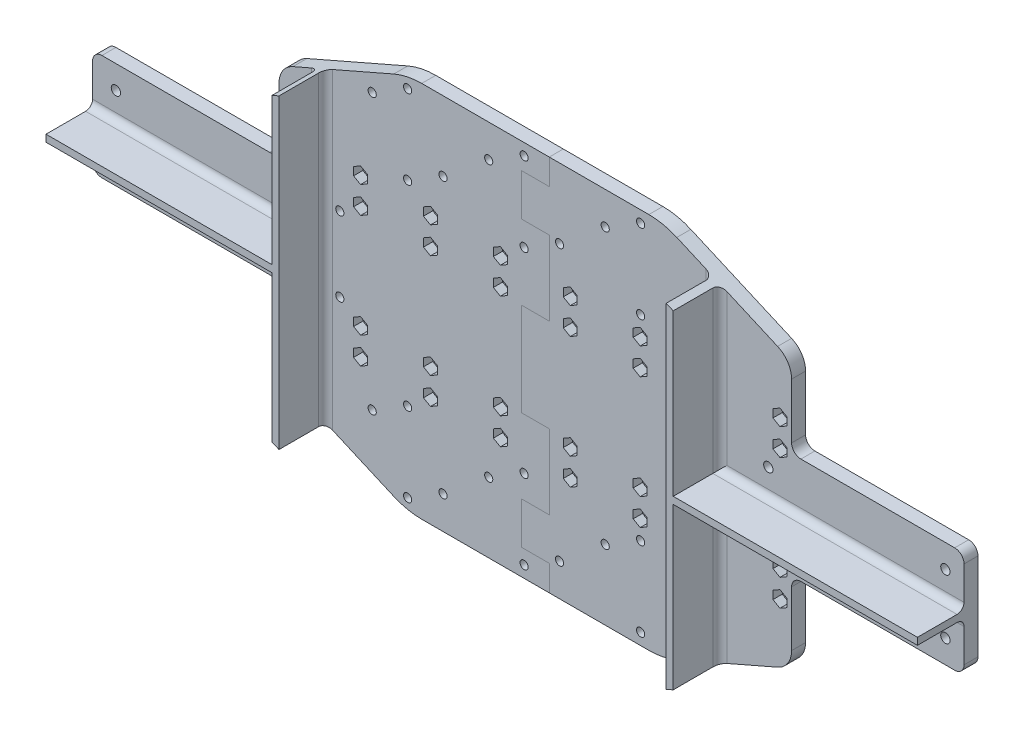
SolidWorks part; units mm, degrees
ref_plane "Top Plane" through (0, 0, 0) normal (0, 0, 1) x (1, 0, 0)
ref_plane "Right Plane" through (0, 0, 0) normal (0, 1, 0) x (1, 0, 0)
ref_plane "Front Plane" through (0, 0, 0) normal (1, 0, 0) x (0, 0, -1)
sketch "Sketch1" plane through (0, 0, 0) normal (0, 0, 1) x (1, 0, 0)
  line L0 (-187, 81) -> (187, -81) construction
  line L1 (-187, 81) -> (187, 81) construction
  line L2 (-187, 81) -> (-187, -81) construction
  line L3 (-187, -81) -> (187, -81) construction
  line L4 (187, 81) -> (187, -81) construction
  line L5 (-187, -22.75) -> (-107, -22.75) construction
  line L6 (-107, -22.75) -> (-107, -81) construction
  line L7 (113, -81) -> (113, -22.75) construction
  line L8 (113, -22.75) -> (187, -22.75) construction
  line L9 (-187, 0) -> (187, 0) construction
  line L10 (113, 22.75) -> (187, 22.75) construction
  line L11 (113, 81) -> (113, 22.75) construction
  line L12 (-107, 22.75) -> (-107, 81) construction
  line L13 (-187, 22.75) -> (-107, 22.75) construction
  line L14 (85.2, -81) -> (85.2, 81) construction
  line L15 (-93, -81) -> (-93, 81) construction
  line L16 (-187, -2.75) -> (187, -2.75) construction
  line L17 (187, 2.75) -> (-187, 2.75) construction
  text T0 "FRONT" font "Century Gothic" height in points 80
  dimension "D1" = 374
  dimension "D2" = 162
  dimension "D3" = 45.5
  dimension "D4" = 80
  dimension "D5" = 74
  dimension "D6" = 27.8
  dimension "D7" = 14
  dimension "D8" = 20
  dimension "D9" = 20
sketch "Sketch2" plane through (0, 0, 0) normal (0, 0, 1) x (1, 0, 0)
  line L0 (-187, 81) -> (-187, -81) construction
  line L1 (-187, 81) -> (187, 81) construction
  line L2 (187, 81) -> (187, -81) construction
  line L3 (-187, -81) -> (187, -81) construction
  line L4 (113, -81) -> (113, -22.75) construction
  line L5 (113, -22.75) -> (187, -22.75) construction
  line L6 (113, 22.75) -> (187, 22.75) construction
  line L7 (113, 81) -> (113, 22.75) construction
  line L8 (-107, 22.75) -> (-107, 81) construction
  line L9 (-187, 22.75) -> (-107, 22.75) construction
  line L10 (-107, -22.75) -> (-107, -81) construction
  line L11 (-187, -22.75) -> (-107, -22.75) construction
  line L12 (-187, 22.75) -> (-187, -22.75)
  line L13 (-107, 81) -> (113, 81)
  line L14 (187, 22.75) -> (187, -22.75)
  line L15 (-107, -81) -> (113, -81)
  line L16 (113, -81) -> (113, -22.75)
  line L17 (113, -22.75) -> (187, -22.75)
  line L18 (113, 22.75) -> (187, 22.75)
  line L19 (113, 81) -> (113, 22.75)
  line L20 (-107, 22.75) -> (-107, 81)
  line L21 (-187, 22.75) -> (-107, 22.75)
  line L22 (-107, -22.75) -> (-107, -81)
  line L23 (-187, -22.75) -> (-107, -22.75)
extrude "Boss-Extrude1" add sketch "Sketch2" along normal mid plane 6
sketch "Sketch3" plane through (0, 0, 3) normal (0, 0, 1) x (1, 0, 0)
  line L0 (-187, -1.5) -> (-90, -1.5)
  line L1 (-187, 81) -> (-187, -81) construction
  line L2 (187, 81) -> (187, -81) construction
  line L3 (-187, 0) -> (187, 0) construction
  line L4 (-187, 0) -> (187, 0) construction
  line L5 (-187, 1.5) -> (-90, 1.5)
  line L6 (-90, 81) -> (-90, 1.5)
  line L7 (-187, 81) -> (187, 81) construction
  line L8 (82.2, -81) -> (82.2, -1.5)
  line L9 (85.2, -81) -> (85.2, 81) construction
  line L10 (-93, -81) -> (-93, 81) construction
  line L11 (-87, -81) -> (-87, 81)
  line L12 (-187, -81) -> (187, -81) construction
  line L13 (79.2, -81) -> (79.2, 81)
  line L14 (79.2, -81) -> (82.2, -81)
  line L15 (79.2, 81) -> (82.2, 81)
  line L16 (-90, 81) -> (-87, 81)
  line L17 (-90, -81) -> (-87, -81)
  line L20 (82.2, 1.5) -> (187, 1.5)
  line L21 (82.2, -1.5) -> (187, -1.5)
  line L22 (82.2, 1.5) -> (82.2, 81)
  line L23 (-90, -1.5) -> (-90, -81)
  line L24 (187, -1.5) -> (187, 1.5)
  line L25 (-187, -1.5) -> (-187, 1.5)
  point P34 (-87, 0)
  point P35 (79.2, 0)
  dimension "D1" = 3
  dimension "D2" = 3
  dimension "D3" = 3
  dimension "D4" = 3
extrude "Boss-Extrude2" add sketch "Sketch3" along normal blind 20
sketch "Sketch4" plane through (0, 0, 3) normal (0, 0, 1) x (1, 0, 0)
  line L0 (-17, -67) -> (13.4, -67) construction
  line L1 (-67, -67) -> (-36.6, -67) construction
  line L2 (-67, -67) -> (-67, -51) construction
  line L3 (-67, -51) -> (-36.6, -51) construction
  line L4 (-36.6, -67) -> (-36.6, -51) construction
  line L5 (-17, -67) -> (-17, -51) construction
  line L6 (-17, -51) -> (13.4, -51) construction
  line L7 (13.4, -67) -> (13.4, -51) construction
  line L8 (33, -67) -> (63.4, -67) construction
  line L9 (33, -67) -> (33, -51) construction
  line L10 (33, -51) -> (63.4, -51) construction
  line L11 (63.4, -67) -> (63.4, -51) construction
  line L12 (-36.6, -67) -> (13.4, -67) construction
  line L13 (-107, -22.75) -> (-107, -81) construction
  line L14 (-67, 59) -> (63.4, 59) construction
  line L15 (-187, -81) -> (187, -81) construction
  line L16 (-187, 0) -> (187, 0) construction
  line L17 (-187, 0) -> (187, 0) construction
  line L18 (-36.6, 67) -> (13.4, 67) construction
  line L19 (63.4, 67) -> (63.4, 51) construction
  line L20 (33, 51) -> (63.4, 51) construction
  line L21 (33, 67) -> (33, 51) construction
  line L22 (33, 67) -> (63.4, 67) construction
  line L23 (13.4, 67) -> (13.4, 51) construction
  line L24 (-17, 51) -> (13.4, 51) construction
  line L25 (-17, 67) -> (-17, 51) construction
  line L26 (-36.6, 67) -> (-36.6, 51) construction
  line L27 (-67, 51) -> (-36.6, 51) construction
  line L28 (-67, 67) -> (-67, 51) construction
  line L29 (-67, 67) -> (-36.6, 67) construction
  line L30 (-17, 67) -> (13.4, 67) construction
  circle A0 centre (-36.6, -67) radius 1.75
  circle A1 centre (-67, -51) radius 1.75
  circle A2 centre (13.4, -67) radius 1.75
  circle A3 centre (-17, -51) radius 1.75
  circle A4 centre (63.4, -67) radius 1.75
  circle A5 centre (33, -51) radius 1.75
  circle A6 centre (33, 51) radius 1.75 construction
  circle A7 centre (63.4, 67) radius 1.75 construction
  circle A8 centre (-17, 51) radius 1.75 construction
  circle A9 centre (13.4, 67) radius 1.75 construction
  circle A10 centre (-67, 51) radius 1.75 construction
  circle A11 centre (-36.6, 67) radius 1.75 construction
  circle A12 centre (33, 67) radius 1.75
  circle A13 centre (63.4, 51) radius 1.75
  circle A14 centre (13.4, 51) radius 1.75
  circle A15 centre (-17, 67) radius 1.75
  circle A16 centre (-36.6, 51) radius 1.75
  circle A17 centre (-67, 67) radius 1.75
  dimension "D3" = 3.5
  dimension "D1" = 16
  dimension "D2" = 30.4
  dimension "D5" = 50
  dimension "D6" = 40
  dimension "D7" = 14
  dimension "D4" = 3
extrude "Cut-Extrude1" cut sketch "Sketch4" against normal through all
fillet "Fillet1" radius 4 4 edges at (-107, 22.75, 0) (-107, -22.75, 0) (113, -22.75, 0) (113, 22.75, 0)
fillet "Fillet2" radius 3 10 edges at (-90, 41.25, 3) (-138.5, 1.5, 3) (-138.5, -1.5, 3) (-90, -41.25, 3) (82.2, -41.25, 3) (134.6, -1.5, 3) (134.6, 1.5, 3) (82.2, 41.25, 3) (-87, 0, 3) (79.2, 0, 3)
sketch "Sketch5" plane through (0, 0, -3) normal (0, 0, -1) x (-1, 0, 0)
  circle A0 centre (-103, -12.75) radius 2 construction
  circle A1 centre (-103, 12.75) radius 2 construction
  circle A2 centre (-179, 12.75) radius 2 construction
  circle A3 centre (-179, -12.75) radius 2 construction
  circle A4 centre (177, 12.75) radius 2 construction
  circle A5 centre (177, -12.75) radius 2 construction
  circle A6 centre (101, -12.75) radius 2 construction
  circle A7 centre (101, 12.75) radius 2 construction
  circle A8 centre (-103, -12.75) radius 2
  circle A9 centre (-103, 12.75) radius 2
  circle A10 centre (-179, 12.75) radius 2
  circle A11 centre (-179, -12.75) radius 2
  circle A12 centre (177, 12.75) radius 2
  circle A13 centre (177, -12.75) radius 2
  circle A14 centre (101, -12.75) radius 2
  circle A15 centre (101, 12.75) radius 2
extrude "Cut-Extrude2" cut sketch "Sketch5" against normal up to next
sketch "Sketch6" plane through (0, 0, 3) normal (0, 0, 1) x (1, 0, 0)
  line L0 (-67, -67) -> (-36.6, -51) construction
  line L1 (-51.8, -76) -> (-51.8, -42) construction
  line L2 (-67, -59) -> (-36.6, -59) construction
  line L3 (-67, -67) -> (-67, -51) construction
  line L4 (-36.6, -67) -> (-36.6, -51) construction
  line L5 (-1.8, -76) -> (-1.8, -42) construction
  line L6 (48.2, -76) -> (48.2, -42) construction
  line L7 (-51.8, -59) -> (-1.8, -59) construction
  line L8 (-187, 0) -> (187, 0) construction
  line L9 (-187, 0) -> (187, 0) construction
  line L10 (-51.8, 59) -> (-1.8, 59) construction
  line L11 (48.2, 76) -> (48.2, 42) construction
  line L12 (-1.8, 76) -> (-1.8, 42) construction
  line L13 (-67, 59) -> (-36.6, 59) construction
  line L14 (-51.8, 76) -> (-51.8, 42) construction
  line L15 (-67, 67) -> (-36.6, 51) construction
  circle A0 centre (-51.8, -76) radius 1.75
  circle A1 centre (-51.8, -42) radius 1.75
  circle A2 centre (-1.8, -76) radius 1.75
  circle A3 centre (-1.8, -42) radius 1.75
  circle A4 centre (48.2, -76) radius 1.75
  circle A5 centre (48.2, -42) radius 1.75
  circle A6 centre (48.2, 42) radius 1.75
  circle A7 centre (48.2, 76) radius 1.75
  circle A8 centre (-1.8, 42) radius 1.75
  circle A9 centre (-1.8, 76) radius 1.75
  circle A10 centre (-51.8, 42) radius 1.75
  circle A11 centre (-51.8, 76) radius 1.75
  point P4 (-51.8, -59)
  point P17 (-1.8, -59)
  point P22 (48.2, -59)
  point P47 (48.2, 59)
  dimension "D1" = 3.5
  dimension "D2" = 34
  dimension "D4" = 50
  dimension "D3" = 3
extrude "Cut-Extrude3" cut sketch "Sketch6" against normal through all
sketch "Sketch8" plane through (0, 0, 3) normal (0, 0, 1) x (1, 0, 0)
  line L0 (-80.9, -16) -> (73.1, 16) construction
  line L1 (-80.9, -16) -> (73.1, -16) construction
  line L2 (-80.9, -16) -> (-80.9, 16) construction
  line L3 (-80.9, 16) -> (73.1, 16) construction
  line L4 (73.1, -16) -> (73.1, 16) construction
  line L5 (-187, 0) -> (187, 0) construction
  line L6 (-187, 0) -> (187, 0) construction
  line L7 (-3.9, -21.9049) -> (-3.9, 21.9049) construction
  line L8 (-93, -81) -> (85.2, 81) construction
  circle A0 centre (-80.9, -16) radius 1.75
  circle A1 centre (-80.9, 16) radius 1.75
  circle A2 centre (73.1, 16) radius 1.75
  circle A3 centre (73.1, -16) radius 1.75
  point P7 (-3.9, 0)
  dimension "D3" = 3.5
  dimension "D1" = 32
  dimension "D2" = 154
extrude "Cut-Extrude5" cut sketch "Sketch8" against normal through all
sketch "Sketch9" plane through (0, 0, 3) normal (0, 0, 1) x (1, 0, 0)
  line L0 (-107.9535, -28) -> (101.269, -28) construction
  line L1 (-12, -33.75) -> (18, -33.75) construction
  line L2 (-12, -22.25) -> (-42, -22.25) construction
  line L3 (-12, -22.25) -> (18, -22.25) construction
  line L4 (-194.5845, 0) -> (205.1662, 0) construction
  line L5 (3, -92.4344) -> (3, 92.4344) construction
  line L6 (-12, -33.75) -> (-42, -33.75) construction
  line L7 (-107, 81) -> (113, -81) construction
  line L8 (-45, -32.0179) -> (-45, -35.4821) construction
  line L9 (-15, -35.4821) -> (-12, -37.2141) construction
  line L10 (-12, -37.2141) -> (-9, -35.4821) construction
  line L11 (-9, -35.4821) -> (-9, -32.0179) construction
  line L12 (-9, -32.0179) -> (-12, -30.2859) construction
  line L13 (-12, -30.2859) -> (-15, -32.0179) construction
  line L14 (-15, -32.0179) -> (-15, -35.4821) construction
  line L15 (-45, -35.4821) -> (-42, -37.2141) construction
  line L16 (-42, -37.2141) -> (-39, -35.4821) construction
  line L17 (-39, -35.4821) -> (-39, -32.0179) construction
  line L18 (-39, -32.0179) -> (-42, -30.2859) construction
  line L19 (-42, -30.2859) -> (-45, -32.0179) construction
  line L20 (-75, -32.0179) -> (-75, -35.4821) construction
  line L21 (-75, -35.4821) -> (-72, -37.2141) construction
  line L22 (-72, -37.2141) -> (-69, -35.4821) construction
  line L23 (-69, -35.4821) -> (-69, -32.0179) construction
  line L24 (-69, -32.0179) -> (-72, -30.2859) construction
  line L25 (-72, -30.2859) -> (-75, -32.0179) construction
  line L26 (-105, -32.0179) -> (-105, -35.4821) construction
  line L27 (-105, -35.4821) -> (-102, -37.2141) construction
  line L28 (-102, -37.2141) -> (-99, -35.4821) construction
  line L29 (-99, -35.4821) -> (-99, -32.0179) construction
  line L30 (-99, -32.0179) -> (-102, -30.2859) construction
  line L31 (-102, -30.2859) -> (-105, -32.0179) construction
  line L32 (-45, -35.4821) -> (-39, -32.0179) construction
  line L33 (-42, -33.75) -> (-12, -33.75) construction
  line L34 (-12, -25.7141) -> (-15, -23.9821) construction
  line L35 (-9, -23.9821) -> (-12, -25.7141) construction
  line L36 (-9, -20.5179) -> (-9, -23.9821) construction
  line L37 (-12, -18.7859) -> (-9, -20.5179) construction
  line L38 (-15, -20.5179) -> (-12, -18.7859) construction
  line L39 (-15, -23.9821) -> (-15, -20.5179) construction
  line L40 (-39, -20.5179) -> (-39, -23.9821) construction
  line L41 (-42, -18.7859) -> (-39, -20.5179) construction
  line L42 (-45, -20.5179) -> (-42, -18.7859) construction
  line L43 (-45, -23.9821) -> (-45, -20.5179) construction
  line L44 (-42, -25.7141) -> (-45, -23.9821) construction
  line L45 (-39, -23.9821) -> (-42, -25.7141) construction
  line L46 (-69, -20.5179) -> (-69, -23.9821) construction
  line L47 (-72, -18.7859) -> (-69, -20.5179) construction
  line L48 (-75, -20.5179) -> (-72, -18.7859) construction
  line L49 (-75, -23.9821) -> (-75, -20.5179) construction
  line L50 (-72, -25.7141) -> (-75, -23.9821) construction
  line L51 (-69, -23.9821) -> (-72, -25.7141) construction
  line L52 (-99, -20.5179) -> (-99, -23.9821) construction
  line L53 (-102, -18.7859) -> (-99, -20.5179) construction
  line L54 (-105, -20.5179) -> (-102, -18.7859) construction
  line L55 (-105, -23.9821) -> (-105, -20.5179) construction
  line L56 (-102, -25.7141) -> (-105, -23.9821) construction
  line L57 (-99, -23.9821) -> (-102, -25.7141) construction
  line L58 (105, -23.9821) -> (108, -25.7141) construction
  line L59 (108, -25.7141) -> (111, -23.9821) construction
  line L60 (111, -23.9821) -> (111, -20.5179) construction
  line L61 (111, -20.5179) -> (108, -18.7859) construction
  line L62 (108, -18.7859) -> (105, -20.5179) construction
  line L63 (105, -20.5179) -> (105, -23.9821) construction
  line L64 (75, -23.9821) -> (78, -25.7141) construction
  line L65 (78, -25.7141) -> (81, -23.9821) construction
  line L66 (81, -23.9821) -> (81, -20.5179) construction
  line L67 (81, -20.5179) -> (78, -18.7859) construction
  line L68 (78, -18.7859) -> (75, -20.5179) construction
  line L69 (75, -20.5179) -> (75, -23.9821) construction
  line L70 (45, -23.9821) -> (48, -25.7141) construction
  line L71 (48, -25.7141) -> (51, -23.9821) construction
  line L72 (51, -23.9821) -> (51, -20.5179) construction
  line L73 (51, -20.5179) -> (48, -18.7859) construction
  line L74 (48, -18.7859) -> (45, -20.5179) construction
  line L75 (45, -20.5179) -> (45, -23.9821) construction
  line L76 (21, -23.9821) -> (21, -20.5179) construction
  line L77 (21, -20.5179) -> (18, -18.7859) construction
  line L78 (18, -18.7859) -> (15, -20.5179) construction
  line L79 (15, -20.5179) -> (15, -23.9821) construction
  line L80 (15, -23.9821) -> (18, -25.7141) construction
  line L81 (18, -25.7141) -> (21, -23.9821) construction
  line L82 (48, -33.75) -> (18, -33.75) construction
  line L83 (51, -35.4821) -> (45, -32.0179) construction
  line L84 (108, -30.2859) -> (111, -32.0179) construction
  line L85 (105, -32.0179) -> (108, -30.2859) construction
  line L86 (105, -35.4821) -> (105, -32.0179) construction
  line L87 (108, -37.2141) -> (105, -35.4821) construction
  line L88 (111, -35.4821) -> (108, -37.2141) construction
  line L89 (111, -32.0179) -> (111, -35.4821) construction
  line L90 (78, -30.2859) -> (81, -32.0179) construction
  line L91 (75, -32.0179) -> (78, -30.2859) construction
  line L92 (75, -35.4821) -> (75, -32.0179) construction
  line L93 (78, -37.2141) -> (75, -35.4821) construction
  line L94 (81, -35.4821) -> (78, -37.2141) construction
  line L95 (81, -32.0179) -> (81, -35.4821) construction
  line L96 (48, -30.2859) -> (51, -32.0179) construction
  line L97 (45, -32.0179) -> (48, -30.2859) construction
  line L98 (45, -35.4821) -> (45, -32.0179) construction
  line L99 (48, -37.2141) -> (45, -35.4821) construction
  line L100 (51, -35.4821) -> (48, -37.2141) construction
  line L101 (21, -32.0179) -> (21, -35.4821) construction
  line L102 (18, -30.2859) -> (21, -32.0179) construction
  line L103 (15, -32.0179) -> (18, -30.2859) construction
  line L104 (15, -35.4821) -> (15, -32.0179) construction
  line L105 (18, -37.2141) -> (15, -35.4821) construction
  line L106 (21, -35.4821) -> (18, -37.2141) construction
  line L107 (51, -32.0179) -> (51, -35.4821) construction
  line L108 (51, 32.0179) -> (51, 35.4821) construction
  line L109 (21, 35.4821) -> (18, 37.2141) construction
  line L110 (18, 37.2141) -> (15, 35.4821) construction
  line L111 (15, 35.4821) -> (15, 32.0179) construction
  line L112 (15, 32.0179) -> (18, 30.2859) construction
  line L113 (18, 30.2859) -> (21, 32.0179) construction
  line L114 (21, 32.0179) -> (21, 35.4821) construction
  line L115 (51, 35.4821) -> (48, 37.2141) construction
  line L116 (48, 37.2141) -> (45, 35.4821) construction
  line L117 (45, 35.4821) -> (45, 32.0179) construction
  line L118 (45, 32.0179) -> (48, 30.2859) construction
  line L119 (48, 30.2859) -> (51, 32.0179) construction
  line L120 (81, 32.0179) -> (81, 35.4821) construction
  line L121 (81, 35.4821) -> (78, 37.2141) construction
  line L122 (78, 37.2141) -> (75, 35.4821) construction
  line L123 (75, 35.4821) -> (75, 32.0179) construction
  line L124 (75, 32.0179) -> (78, 30.2859) construction
  line L125 (78, 30.2859) -> (81, 32.0179) construction
  line L126 (111, 32.0179) -> (111, 35.4821) construction
  line L127 (111, 35.4821) -> (108, 37.2141) construction
  line L128 (108, 37.2141) -> (105, 35.4821) construction
  line L129 (105, 35.4821) -> (105, 32.0179) construction
  line L130 (105, 32.0179) -> (108, 30.2859) construction
  line L131 (108, 30.2859) -> (111, 32.0179) construction
  line L132 (51, 35.4821) -> (45, 32.0179) construction
  line L133 (48, 33.75) -> (18, 33.75) construction
  line L134 (18, 25.7141) -> (21, 23.9821) construction
  line L135 (15, 23.9821) -> (18, 25.7141) construction
  line L136 (15, 20.5179) -> (15, 23.9821) construction
  line L137 (18, 18.7859) -> (15, 20.5179) construction
  line L138 (21, 20.5179) -> (18, 18.7859) construction
  line L139 (21, 23.9821) -> (21, 20.5179) construction
  line L140 (45, 20.5179) -> (45, 23.9821) construction
  line L141 (48, 18.7859) -> (45, 20.5179) construction
  line L142 (51, 20.5179) -> (48, 18.7859) construction
  line L143 (51, 23.9821) -> (51, 20.5179) construction
  line L144 (48, 25.7141) -> (51, 23.9821) construction
  line L145 (45, 23.9821) -> (48, 25.7141) construction
  line L146 (75, 20.5179) -> (75, 23.9821) construction
  line L147 (78, 18.7859) -> (75, 20.5179) construction
  line L148 (81, 20.5179) -> (78, 18.7859) construction
  line L149 (81, 23.9821) -> (81, 20.5179) construction
  line L150 (78, 25.7141) -> (81, 23.9821) construction
  line L151 (75, 23.9821) -> (78, 25.7141) construction
  line L152 (105, 20.5179) -> (105, 23.9821) construction
  line L153 (108, 18.7859) -> (105, 20.5179) construction
  line L154 (111, 20.5179) -> (108, 18.7859) construction
  line L155 (111, 23.9821) -> (111, 20.5179) construction
  line L156 (108, 25.7141) -> (111, 23.9821) construction
  line L157 (105, 23.9821) -> (108, 25.7141) construction
  line L158 (-99, 23.9821) -> (-102, 25.7141) construction
  line L159 (-102, 25.7141) -> (-105, 23.9821) construction
  line L160 (-105, 23.9821) -> (-105, 20.5179) construction
  line L161 (-105, 20.5179) -> (-102, 18.7859) construction
  line L162 (-102, 18.7859) -> (-99, 20.5179) construction
  line L163 (-99, 20.5179) -> (-99, 23.9821) construction
  line L164 (-69, 23.9821) -> (-72, 25.7141) construction
  line L165 (-72, 25.7141) -> (-75, 23.9821) construction
  line L166 (-75, 23.9821) -> (-75, 20.5179) construction
  line L167 (-75, 20.5179) -> (-72, 18.7859) construction
  line L168 (-72, 18.7859) -> (-69, 20.5179) construction
  line L169 (-69, 20.5179) -> (-69, 23.9821) construction
  line L170 (-39, 23.9821) -> (-42, 25.7141) construction
  line L171 (-42, 25.7141) -> (-45, 23.9821) construction
  line L172 (-45, 23.9821) -> (-45, 20.5179) construction
  line L173 (-45, 20.5179) -> (-42, 18.7859) construction
  line L174 (-42, 18.7859) -> (-39, 20.5179) construction
  line L175 (-39, 20.5179) -> (-39, 23.9821) construction
  line L176 (-15, 23.9821) -> (-15, 20.5179) construction
  line L177 (-15, 20.5179) -> (-12, 18.7859) construction
  line L178 (-12, 18.7859) -> (-9, 20.5179) construction
  line L179 (-9, 20.5179) -> (-9, 23.9821) construction
  line L180 (-9, 23.9821) -> (-12, 25.7141) construction
  line L181 (-12, 25.7141) -> (-15, 23.9821) construction
  line L182 (-42, 33.75) -> (-12, 33.75) construction
  line L183 (-45, 35.4821) -> (-39, 32.0179) construction
  line L184 (-102, 30.2859) -> (-105, 32.0179) construction
  line L185 (-99, 32.0179) -> (-102, 30.2859) construction
  line L186 (-99, 35.4821) -> (-99, 32.0179) construction
  line L187 (-102, 37.2141) -> (-99, 35.4821) construction
  line L188 (-105, 35.4821) -> (-102, 37.2141) construction
  line L189 (-105, 32.0179) -> (-105, 35.4821) construction
  line L190 (-72, 30.2859) -> (-75, 32.0179) construction
  line L191 (-69, 32.0179) -> (-72, 30.2859) construction
  line L192 (-69, 35.4821) -> (-69, 32.0179) construction
  line L193 (-72, 37.2141) -> (-69, 35.4821) construction
  line L194 (-75, 35.4821) -> (-72, 37.2141) construction
  line L195 (-75, 32.0179) -> (-75, 35.4821) construction
  line L196 (-42, 30.2859) -> (-45, 32.0179) construction
  line L197 (-39, 32.0179) -> (-42, 30.2859) construction
  line L198 (-39, 35.4821) -> (-39, 32.0179) construction
  line L199 (-42, 37.2141) -> (-39, 35.4821) construction
  line L200 (-45, 35.4821) -> (-42, 37.2141) construction
  line L201 (-15, 32.0179) -> (-15, 35.4821) construction
  line L202 (-12, 30.2859) -> (-15, 32.0179) construction
  line L203 (-9, 32.0179) -> (-12, 30.2859) construction
  line L204 (-9, 35.4821) -> (-9, 32.0179) construction
  line L205 (-12, 37.2141) -> (-9, 35.4821) construction
  line L206 (-15, 35.4821) -> (-12, 37.2141) construction
  line L207 (-45, 32.0179) -> (-45, 35.4821) construction
  line L208 (-12, 33.75) -> (-42, 33.75) construction
  line L209 (-12, 22.25) -> (18, 22.25) construction
  line L210 (-12, 22.25) -> (-42, 22.25) construction
  line L211 (-12, 33.75) -> (18, 33.75) construction
  line L212 (-107.9535, 28) -> (101.269, 28) construction
  circle A0 centre (-12, -33.75) radius 1.75
  circle A1 centre (-42, -33.75) radius 1.75
  circle A2 centre (-72, -33.75) radius 1.75
  circle A3 centre (-102, -33.75) radius 1.75
  circle A4 centre (108, -33.75) radius 1.75
  circle A5 centre (78, -33.75) radius 1.75 construction
  circle A6 centre (48, -33.75) radius 1.75
  circle A7 centre (18, -33.75) radius 1.75
  circle A8 centre (18, -22.25) radius 1.75
  circle A9 centre (48, -22.25) radius 1.75
  circle A10 centre (78, -22.25) radius 1.75 construction
  circle A11 centre (108, -22.25) radius 1.75
  circle A12 centre (-102, -22.25) radius 1.75
  circle A13 centre (-72, -22.25) radius 1.75
  circle A14 centre (-42, -22.25) radius 1.75
  circle A15 centre (-12, -22.25) radius 1.75
  circle A16 centre (-12, -33.75) radius 3 construction
  circle A17 centre (-12, 33.75) radius 3 construction
  circle A18 centre (-12, 22.25) radius 1.75
  circle A19 centre (-42, 22.25) radius 1.75
  circle A20 centre (-72, 22.25) radius 1.75
  circle A21 centre (-102, 22.25) radius 1.75
  circle A22 centre (108, 22.25) radius 1.75
  circle A23 centre (78, 22.25) radius 1.75 construction
  circle A24 centre (48, 22.25) radius 1.75
  circle A25 centre (18, 22.25) radius 1.75
  circle A26 centre (18, 33.75) radius 1.75
  circle A27 centre (48, 33.75) radius 1.75
  circle A28 centre (78, 33.75) radius 1.75 construction
  circle A29 centre (108, 33.75) radius 1.75
  circle A30 centre (-102, 33.75) radius 1.75
  circle A31 centre (-72, 33.75) radius 1.75
  circle A32 centre (-42, 33.75) radius 1.75
  circle A33 centre (-12, 33.75) radius 1.75
  point P6 (3, -33.75)
  point P39 (3, -22.25)
  point P46 (3, 0)
  point P277 (3, 22.25)
  point P278 (3, 33.75)
  dimension "D3" = 3.5
  dimension "D1" = 11.5
  dimension "D2" = 28
  dimension "D5" = 30
  dimension "D6" = 6
  dimension "D4" = 4
  dimension "D7" = 4
extrude "Cut-Extrude6" cut sketch "Sketch9" against normal through all
sketch "Sketch10" plane through (0, 0, 3) normal (0, 0, 1) x (1, 0, 0)
  line L0 (-99, -35.4821) -> (-99, -32.0179) construction
  line L1 (-102, -37.2141) -> (-99, -35.4821) construction
  line L2 (-105, -35.4821) -> (-102, -37.2141) construction
  line L3 (-105, -32.0179) -> (-105, -35.4821) construction
  line L4 (-102, -30.2859) -> (-105, -32.0179) construction
  line L5 (-99, -32.0179) -> (-102, -30.2859) construction
  line L6 (-99, -35.4821) -> (-99, -32.0179)
  line L7 (-102, -37.2141) -> (-99, -35.4821)
  line L8 (-105, -35.4821) -> (-102, -37.2141)
  line L9 (-105, -32.0179) -> (-105, -35.4821)
  line L10 (-102, -30.2859) -> (-105, -32.0179)
  line L11 (-99, -32.0179) -> (-102, -30.2859)
  line L12 (-69, -35.4821) -> (-69, -32.0179) construction
  line L13 (-72, -37.2141) -> (-69, -35.4821) construction
  line L14 (-75, -35.4821) -> (-72, -37.2141) construction
  line L15 (-75, -32.0179) -> (-75, -35.4821) construction
  line L16 (-72, -30.2859) -> (-75, -32.0179) construction
  line L17 (-69, -32.0179) -> (-72, -30.2859) construction
  line L18 (-69, -35.4821) -> (-69, -32.0179)
  line L19 (-72, -37.2141) -> (-69, -35.4821)
  line L20 (-75, -35.4821) -> (-72, -37.2141)
  line L21 (-75, -32.0179) -> (-75, -35.4821)
  line L22 (-72, -30.2859) -> (-75, -32.0179)
  line L23 (-69, -32.0179) -> (-72, -30.2859)
  line L24 (-39, -35.4821) -> (-39, -32.0179) construction
  line L25 (-42, -37.2141) -> (-39, -35.4821) construction
  line L26 (-45, -35.4821) -> (-42, -37.2141) construction
  line L27 (-45, -32.0179) -> (-45, -35.4821) construction
  line L28 (-42, -30.2859) -> (-45, -32.0179) construction
  line L29 (-39, -32.0179) -> (-42, -30.2859) construction
  line L30 (-39, -35.4821) -> (-39, -32.0179)
  line L31 (-42, -37.2141) -> (-39, -35.4821)
  line L32 (-45, -35.4821) -> (-42, -37.2141)
  line L33 (-45, -32.0179) -> (-45, -35.4821)
  line L34 (-42, -30.2859) -> (-45, -32.0179)
  line L35 (-39, -32.0179) -> (-42, -30.2859)
  line L36 (-9, -35.4821) -> (-9, -32.0179) construction
  line L37 (-12, -37.2141) -> (-9, -35.4821) construction
  line L38 (-15, -35.4821) -> (-12, -37.2141) construction
  line L39 (-15, -32.0179) -> (-15, -35.4821) construction
  line L40 (-12, -30.2859) -> (-15, -32.0179) construction
  line L41 (-9, -32.0179) -> (-12, -30.2859) construction
  line L42 (-9, -35.4821) -> (-9, -32.0179)
  line L43 (-12, -37.2141) -> (-9, -35.4821)
  line L44 (-15, -35.4821) -> (-12, -37.2141)
  line L45 (-15, -32.0179) -> (-15, -35.4821)
  line L46 (-12, -30.2859) -> (-15, -32.0179)
  line L47 (-9, -32.0179) -> (-12, -30.2859)
  line L48 (75, -35.4821) -> (75, -32.0179) construction
  line L49 (78, -37.2141) -> (75, -35.4821) construction
  line L50 (81, -35.4821) -> (78, -37.2141) construction
  line L51 (81, -32.0179) -> (81, -35.4821) construction
  line L52 (78, -30.2859) -> (81, -32.0179) construction
  line L53 (75, -32.0179) -> (78, -30.2859) construction
  line L54 (51, -32.0179) -> (51, -35.4821) construction
  line L55 (48, -30.2859) -> (51, -32.0179) construction
  line L56 (45, -32.0179) -> (48, -30.2859) construction
  line L57 (15, -32.0179) -> (18, -30.2859) construction
  line L58 (15, -35.4821) -> (15, -32.0179) construction
  line L59 (18, -37.2141) -> (15, -35.4821) construction
  line L60 (21, -35.4821) -> (18, -37.2141) construction
  line L61 (21, -32.0179) -> (21, -35.4821) construction
  line L62 (18, -30.2859) -> (21, -32.0179) construction
  line L63 (75, -35.4821) -> (75, -32.0179) construction
  line L64 (78, -37.2141) -> (75, -35.4821) construction
  line L65 (81, -35.4821) -> (78, -37.2141) construction
  line L66 (81, -32.0179) -> (81, -35.4821) construction
  line L67 (78, -30.2859) -> (81, -32.0179) construction
  line L68 (75, -32.0179) -> (78, -30.2859) construction
  line L69 (51, -32.0179) -> (51, -35.4821)
  line L70 (48, -30.2859) -> (51, -32.0179)
  line L71 (45, -32.0179) -> (48, -30.2859)
  line L72 (15, -32.0179) -> (18, -30.2859)
  line L73 (15, -35.4821) -> (15, -32.0179)
  line L74 (18, -37.2141) -> (15, -35.4821)
  line L75 (21, -35.4821) -> (18, -37.2141)
  line L76 (21, -32.0179) -> (21, -35.4821)
  line L77 (18, -30.2859) -> (21, -32.0179)
  line L78 (45, -35.4821) -> (45, -32.0179) construction
  line L79 (48, -37.2141) -> (45, -35.4821) construction
  line L80 (51, -35.4821) -> (48, -37.2141) construction
  line L81 (45, -35.4821) -> (45, -32.0179)
  line L82 (48, -37.2141) -> (45, -35.4821)
  line L83 (51, -35.4821) -> (48, -37.2141)
  line L84 (51, -23.9821) -> (51, -20.5179) construction
  line L85 (48, -25.7141) -> (51, -23.9821) construction
  line L86 (45, -23.9821) -> (48, -25.7141) construction
  line L87 (45, -20.5179) -> (45, -23.9821) construction
  line L88 (48, -18.7859) -> (45, -20.5179) construction
  line L89 (51, -20.5179) -> (48, -18.7859) construction
  line L90 (81, -20.5179) -> (78, -18.7859) construction
  line L91 (81, -23.9821) -> (81, -20.5179) construction
  line L92 (78, -25.7141) -> (81, -23.9821) construction
  line L93 (75, -23.9821) -> (78, -25.7141) construction
  line L94 (75, -20.5179) -> (75, -23.9821) construction
  line L95 (78, -18.7859) -> (75, -20.5179) construction
  line L96 (105, -23.9821) -> (108, -25.7141) construction
  line L97 (105, -20.5179) -> (105, -23.9821) construction
  line L98 (108, -18.7859) -> (105, -20.5179) construction
  line L99 (111, -20.5179) -> (108, -18.7859) construction
  line L100 (111, -23.9821) -> (111, -20.5179) construction
  line L101 (108, -25.7141) -> (111, -23.9821) construction
  line L102 (105, -32.0179) -> (108, -30.2859) construction
  line L103 (105, -35.4821) -> (105, -32.0179) construction
  line L104 (108, -37.2141) -> (105, -35.4821) construction
  line L105 (111, -35.4821) -> (108, -37.2141) construction
  line L106 (111, -32.0179) -> (111, -35.4821) construction
  line L107 (108, -30.2859) -> (111, -32.0179) construction
  line L108 (51, -23.9821) -> (51, -20.5179)
  line L109 (48, -25.7141) -> (51, -23.9821)
  line L110 (45, -23.9821) -> (48, -25.7141)
  line L111 (45, -20.5179) -> (45, -23.9821)
  line L112 (48, -18.7859) -> (45, -20.5179)
  line L113 (51, -20.5179) -> (48, -18.7859)
  line L114 (81, -20.5179) -> (78, -18.7859) construction
  line L115 (81, -23.9821) -> (81, -20.5179) construction
  line L116 (78, -25.7141) -> (81, -23.9821) construction
  line L117 (75, -23.9821) -> (78, -25.7141) construction
  line L118 (75, -20.5179) -> (75, -23.9821) construction
  line L119 (78, -18.7859) -> (75, -20.5179) construction
  line L120 (105, -23.9821) -> (108, -25.7141)
  line L121 (105, -20.5179) -> (105, -23.9821)
  line L122 (108, -18.7859) -> (105, -20.5179)
  line L123 (111, -20.5179) -> (108, -18.7859)
  line L124 (111, -23.9821) -> (111, -20.5179)
  line L125 (108, -25.7141) -> (111, -23.9821)
  line L126 (105, -32.0179) -> (108, -30.2859)
  line L127 (105, -35.4821) -> (105, -32.0179)
  line L128 (108, -37.2141) -> (105, -35.4821)
  line L129 (111, -35.4821) -> (108, -37.2141)
  line L130 (111, -32.0179) -> (111, -35.4821)
  line L131 (108, -30.2859) -> (111, -32.0179)
  line L132 (-45, -20.5179) -> (-42, -18.7859) construction
  line L133 (-45, -23.9821) -> (-45, -20.5179) construction
  line L134 (-42, -25.7141) -> (-45, -23.9821) construction
  line L135 (-39, -23.9821) -> (-42, -25.7141) construction
  line L136 (-39, -20.5179) -> (-39, -23.9821) construction
  line L137 (-42, -18.7859) -> (-39, -20.5179) construction
  line L138 (-15, -20.5179) -> (-12, -18.7859) construction
  line L139 (-15, -23.9821) -> (-15, -20.5179) construction
  line L140 (-12, -25.7141) -> (-15, -23.9821) construction
  line L141 (-9, -23.9821) -> (-12, -25.7141) construction
  line L142 (-9, -20.5179) -> (-9, -23.9821) construction
  line L143 (-12, -18.7859) -> (-9, -20.5179) construction
  line L144 (21, -20.5179) -> (18, -18.7859) construction
  line L145 (21, -23.9821) -> (21, -20.5179) construction
  line L146 (18, -25.7141) -> (21, -23.9821) construction
  line L147 (15, -23.9821) -> (18, -25.7141) construction
  line L148 (15, -20.5179) -> (15, -23.9821) construction
  line L149 (18, -18.7859) -> (15, -20.5179) construction
  line L150 (-45, -20.5179) -> (-42, -18.7859)
  line L151 (-45, -23.9821) -> (-45, -20.5179)
  line L152 (-42, -25.7141) -> (-45, -23.9821)
  line L153 (-39, -23.9821) -> (-42, -25.7141)
  line L154 (-39, -20.5179) -> (-39, -23.9821)
  line L155 (-42, -18.7859) -> (-39, -20.5179)
  line L156 (-15, -20.5179) -> (-12, -18.7859)
  line L157 (-15, -23.9821) -> (-15, -20.5179)
  line L158 (-12, -25.7141) -> (-15, -23.9821)
  line L159 (-9, -23.9821) -> (-12, -25.7141)
  line L160 (-9, -20.5179) -> (-9, -23.9821)
  line L161 (-12, -18.7859) -> (-9, -20.5179)
  line L162 (21, -20.5179) -> (18, -18.7859)
  line L163 (21, -23.9821) -> (21, -20.5179)
  line L164 (18, -25.7141) -> (21, -23.9821)
  line L165 (15, -23.9821) -> (18, -25.7141)
  line L166 (15, -20.5179) -> (15, -23.9821)
  line L167 (18, -18.7859) -> (15, -20.5179)
  line L168 (-105, -23.9821) -> (-105, -20.5179) construction
  line L169 (-102, -25.7141) -> (-105, -23.9821) construction
  line L170 (-99, -23.9821) -> (-102, -25.7141) construction
  line L171 (-99, -20.5179) -> (-99, -23.9821) construction
  line L172 (-102, -18.7859) -> (-99, -20.5179) construction
  line L173 (-105, -20.5179) -> (-102, -18.7859) construction
  line L174 (-72, -25.7141) -> (-75, -23.9821) construction
  line L175 (-69, -23.9821) -> (-72, -25.7141) construction
  line L176 (-69, -20.5179) -> (-69, -23.9821) construction
  line L177 (-72, -18.7859) -> (-69, -20.5179) construction
  line L178 (-75, -20.5179) -> (-72, -18.7859) construction
  line L179 (-75, -23.9821) -> (-75, -20.5179) construction
  line L180 (-105, -23.9821) -> (-105, -20.5179)
  line L181 (-102, -25.7141) -> (-105, -23.9821)
  line L182 (-99, -23.9821) -> (-102, -25.7141)
  line L183 (-99, -20.5179) -> (-99, -23.9821)
  line L184 (-102, -18.7859) -> (-99, -20.5179)
  line L185 (-105, -20.5179) -> (-102, -18.7859)
  line L186 (-72, -25.7141) -> (-75, -23.9821)
  line L187 (-69, -23.9821) -> (-72, -25.7141)
  line L188 (-69, -20.5179) -> (-69, -23.9821)
  line L189 (-72, -18.7859) -> (-69, -20.5179)
  line L190 (-75, -20.5179) -> (-72, -18.7859)
  line L191 (-75, -23.9821) -> (-75, -20.5179)
  line L192 (-69, 20.5179) -> (-69, 23.9821) construction
  line L193 (-72, 18.7859) -> (-69, 20.5179) construction
  line L194 (-75, 20.5179) -> (-72, 18.7859) construction
  line L195 (-75, 23.9821) -> (-75, 20.5179) construction
  line L196 (-72, 25.7141) -> (-75, 23.9821) construction
  line L197 (-69, 23.9821) -> (-72, 25.7141) construction
  line L198 (-75, 35.4821) -> (-72, 37.2141) construction
  line L199 (-75, 32.0179) -> (-75, 35.4821) construction
  line L200 (-72, 30.2859) -> (-75, 32.0179) construction
  line L201 (-69, 32.0179) -> (-72, 30.2859) construction
  line L202 (-69, 35.4821) -> (-69, 32.0179) construction
  line L203 (-72, 37.2141) -> (-69, 35.4821) construction
  line L204 (-99, 20.5179) -> (-99, 23.9821) construction
  line L205 (-102, 18.7859) -> (-99, 20.5179) construction
  line L206 (-105, 20.5179) -> (-102, 18.7859) construction
  line L207 (-105, 23.9821) -> (-105, 20.5179) construction
  line L208 (-102, 25.7141) -> (-105, 23.9821) construction
  line L209 (-99, 23.9821) -> (-102, 25.7141) construction
  line L210 (-105, 35.4821) -> (-102, 37.2141) construction
  line L211 (-105, 32.0179) -> (-105, 35.4821) construction
  line L212 (-102, 30.2859) -> (-105, 32.0179) construction
  line L213 (-99, 32.0179) -> (-102, 30.2859) construction
  line L214 (-99, 35.4821) -> (-99, 32.0179) construction
  line L215 (-102, 37.2141) -> (-99, 35.4821) construction
  line L216 (-69, 20.5179) -> (-69, 23.9821)
  line L217 (-72, 18.7859) -> (-69, 20.5179)
  line L218 (-75, 20.5179) -> (-72, 18.7859)
  line L219 (-75, 23.9821) -> (-75, 20.5179)
  line L220 (-72, 25.7141) -> (-75, 23.9821)
  line L221 (-69, 23.9821) -> (-72, 25.7141)
  line L222 (-75, 35.4821) -> (-72, 37.2141)
  line L223 (-75, 32.0179) -> (-75, 35.4821)
  line L224 (-72, 30.2859) -> (-75, 32.0179)
  line L225 (-69, 32.0179) -> (-72, 30.2859)
  line L226 (-69, 35.4821) -> (-69, 32.0179)
  line L227 (-72, 37.2141) -> (-69, 35.4821)
  line L228 (-99, 20.5179) -> (-99, 23.9821)
  line L229 (-102, 18.7859) -> (-99, 20.5179)
  line L230 (-105, 20.5179) -> (-102, 18.7859)
  line L231 (-105, 23.9821) -> (-105, 20.5179)
  line L232 (-102, 25.7141) -> (-105, 23.9821)
  line L233 (-99, 23.9821) -> (-102, 25.7141)
  line L234 (-105, 35.4821) -> (-102, 37.2141)
  line L235 (-105, 32.0179) -> (-105, 35.4821)
  line L236 (-102, 30.2859) -> (-105, 32.0179)
  line L237 (-99, 32.0179) -> (-102, 30.2859)
  line L238 (-99, 35.4821) -> (-99, 32.0179)
  line L239 (-102, 37.2141) -> (-99, 35.4821)
  line L240 (-12, 18.7859) -> (-9, 20.5179) construction
  line L241 (-15, 20.5179) -> (-12, 18.7859) construction
  line L242 (-15, 23.9821) -> (-15, 20.5179) construction
  line L243 (-12, 25.7141) -> (-15, 23.9821) construction
  line L244 (-9, 23.9821) -> (-12, 25.7141) construction
  line L245 (-9, 20.5179) -> (-9, 23.9821) construction
  line L246 (-15, 35.4821) -> (-12, 37.2141) construction
  line L247 (-15, 32.0179) -> (-15, 35.4821) construction
  line L248 (-12, 30.2859) -> (-15, 32.0179) construction
  line L249 (-9, 32.0179) -> (-12, 30.2859) construction
  line L250 (-9, 35.4821) -> (-9, 32.0179) construction
  line L251 (-12, 37.2141) -> (-9, 35.4821) construction
  line L252 (-39, 20.5179) -> (-39, 23.9821) construction
  line L253 (-42, 18.7859) -> (-39, 20.5179) construction
  line L254 (-45, 20.5179) -> (-42, 18.7859) construction
  line L255 (-45, 23.9821) -> (-45, 20.5179) construction
  line L256 (-42, 25.7141) -> (-45, 23.9821) construction
  line L257 (-39, 23.9821) -> (-42, 25.7141) construction
  line L258 (-45, 32.0179) -> (-45, 35.4821) construction
  line L259 (-42, 30.2859) -> (-45, 32.0179) construction
  line L260 (-39, 32.0179) -> (-42, 30.2859) construction
  line L261 (-39, 35.4821) -> (-39, 32.0179) construction
  line L262 (-42, 37.2141) -> (-39, 35.4821) construction
  line L263 (-45, 35.4821) -> (-42, 37.2141) construction
  line L264 (-12, 18.7859) -> (-9, 20.5179)
  line L265 (-15, 20.5179) -> (-12, 18.7859)
  line L266 (-15, 23.9821) -> (-15, 20.5179)
  line L267 (-12, 25.7141) -> (-15, 23.9821)
  line L268 (-9, 23.9821) -> (-12, 25.7141)
  line L269 (-9, 20.5179) -> (-9, 23.9821)
  line L270 (-15, 35.4821) -> (-12, 37.2141)
  line L271 (-15, 32.0179) -> (-15, 35.4821)
  line L272 (-12, 30.2859) -> (-15, 32.0179)
  line L273 (-9, 32.0179) -> (-12, 30.2859)
  line L274 (-9, 35.4821) -> (-9, 32.0179)
  line L275 (-12, 37.2141) -> (-9, 35.4821)
  line L276 (-39, 20.5179) -> (-39, 23.9821)
  line L277 (-42, 18.7859) -> (-39, 20.5179)
  line L278 (-45, 20.5179) -> (-42, 18.7859)
  line L279 (-45, 23.9821) -> (-45, 20.5179)
  line L280 (-42, 25.7141) -> (-45, 23.9821)
  line L281 (-39, 23.9821) -> (-42, 25.7141)
  line L282 (-45, 32.0179) -> (-45, 35.4821)
  line L283 (-42, 30.2859) -> (-45, 32.0179)
  line L284 (-39, 32.0179) -> (-42, 30.2859)
  line L285 (-39, 35.4821) -> (-39, 32.0179)
  line L286 (-42, 37.2141) -> (-39, 35.4821)
  line L287 (-45, 35.4821) -> (-42, 37.2141)
  line L288 (45, 23.9821) -> (48, 25.7141) construction
  line L289 (45, 20.5179) -> (45, 23.9821) construction
  line L290 (48, 18.7859) -> (45, 20.5179) construction
  line L291 (51, 20.5179) -> (48, 18.7859) construction
  line L292 (51, 23.9821) -> (51, 20.5179) construction
  line L293 (48, 25.7141) -> (51, 23.9821) construction
  line L294 (51, 32.0179) -> (51, 35.4821) construction
  line L295 (48, 30.2859) -> (51, 32.0179) construction
  line L296 (45, 32.0179) -> (48, 30.2859) construction
  line L297 (45, 35.4821) -> (45, 32.0179) construction
  line L298 (48, 37.2141) -> (45, 35.4821) construction
  line L299 (51, 35.4821) -> (48, 37.2141) construction
  line L300 (15, 23.9821) -> (18, 25.7141) construction
  line L301 (15, 20.5179) -> (15, 23.9821) construction
  line L302 (18, 18.7859) -> (15, 20.5179) construction
  line L303 (21, 20.5179) -> (18, 18.7859) construction
  line L304 (21, 23.9821) -> (21, 20.5179) construction
  line L305 (18, 25.7141) -> (21, 23.9821) construction
  line L306 (21, 32.0179) -> (21, 35.4821) construction
  line L307 (18, 30.2859) -> (21, 32.0179) construction
  line L308 (15, 32.0179) -> (18, 30.2859) construction
  line L309 (15, 35.4821) -> (15, 32.0179) construction
  line L310 (18, 37.2141) -> (15, 35.4821) construction
  line L311 (21, 35.4821) -> (18, 37.2141) construction
  line L312 (45, 23.9821) -> (48, 25.7141)
  line L313 (45, 20.5179) -> (45, 23.9821)
  line L314 (48, 18.7859) -> (45, 20.5179)
  line L315 (51, 20.5179) -> (48, 18.7859)
  line L316 (51, 23.9821) -> (51, 20.5179)
  line L317 (48, 25.7141) -> (51, 23.9821)
  line L318 (51, 32.0179) -> (51, 35.4821)
  line L319 (48, 30.2859) -> (51, 32.0179)
  line L320 (45, 32.0179) -> (48, 30.2859)
  line L321 (45, 35.4821) -> (45, 32.0179)
  line L322 (48, 37.2141) -> (45, 35.4821)
  line L323 (51, 35.4821) -> (48, 37.2141)
  line L324 (15, 23.9821) -> (18, 25.7141)
  line L325 (15, 20.5179) -> (15, 23.9821)
  line L326 (18, 18.7859) -> (15, 20.5179)
  line L327 (21, 20.5179) -> (18, 18.7859)
  line L328 (21, 23.9821) -> (21, 20.5179)
  line L329 (18, 25.7141) -> (21, 23.9821)
  line L330 (21, 32.0179) -> (21, 35.4821)
  line L331 (18, 30.2859) -> (21, 32.0179)
  line L332 (15, 32.0179) -> (18, 30.2859)
  line L333 (15, 35.4821) -> (15, 32.0179)
  line L334 (18, 37.2141) -> (15, 35.4821)
  line L335 (21, 35.4821) -> (18, 37.2141)
  line L336 (105, 23.9821) -> (108, 25.7141) construction
  line L337 (105, 20.5179) -> (105, 23.9821) construction
  line L338 (108, 18.7859) -> (105, 20.5179) construction
  line L339 (111, 20.5179) -> (108, 18.7859) construction
  line L340 (111, 23.9821) -> (111, 20.5179) construction
  line L341 (108, 25.7141) -> (111, 23.9821) construction
  line L342 (111, 32.0179) -> (111, 35.4821) construction
  line L343 (108, 30.2859) -> (111, 32.0179) construction
  line L344 (105, 32.0179) -> (108, 30.2859) construction
  line L345 (105, 35.4821) -> (105, 32.0179) construction
  line L346 (108, 37.2141) -> (105, 35.4821) construction
  line L347 (111, 35.4821) -> (108, 37.2141) construction
  line L348 (75, 23.9821) -> (78, 25.7141) construction
  line L349 (75, 20.5179) -> (75, 23.9821) construction
  line L350 (78, 18.7859) -> (75, 20.5179) construction
  line L351 (81, 20.5179) -> (78, 18.7859) construction
  line L352 (81, 23.9821) -> (81, 20.5179) construction
  line L353 (78, 25.7141) -> (81, 23.9821) construction
  line L354 (81, 32.0179) -> (81, 35.4821) construction
  line L355 (78, 30.2859) -> (81, 32.0179) construction
  line L356 (75, 32.0179) -> (78, 30.2859) construction
  line L357 (75, 35.4821) -> (75, 32.0179) construction
  line L358 (78, 37.2141) -> (75, 35.4821) construction
  line L359 (81, 35.4821) -> (78, 37.2141) construction
  line L360 (105, 23.9821) -> (108, 25.7141)
  line L361 (105, 20.5179) -> (105, 23.9821)
  line L362 (108, 18.7859) -> (105, 20.5179)
  line L363 (111, 20.5179) -> (108, 18.7859)
  line L364 (111, 23.9821) -> (111, 20.5179)
  line L365 (108, 25.7141) -> (111, 23.9821)
  line L366 (111, 32.0179) -> (111, 35.4821)
  line L367 (108, 30.2859) -> (111, 32.0179)
  line L368 (105, 32.0179) -> (108, 30.2859)
  line L369 (105, 35.4821) -> (105, 32.0179)
  line L370 (108, 37.2141) -> (105, 35.4821)
  line L371 (111, 35.4821) -> (108, 37.2141)
  line L372 (75, 23.9821) -> (78, 25.7141) construction
  line L373 (75, 20.5179) -> (75, 23.9821) construction
  line L374 (78, 18.7859) -> (75, 20.5179) construction
  line L375 (81, 20.5179) -> (78, 18.7859) construction
  line L376 (81, 23.9821) -> (81, 20.5179) construction
  line L377 (78, 25.7141) -> (81, 23.9821) construction
  line L378 (81, 32.0179) -> (81, 35.4821) construction
  line L379 (78, 30.2859) -> (81, 32.0179) construction
  line L380 (75, 32.0179) -> (78, 30.2859) construction
  line L381 (75, 35.4821) -> (75, 32.0179) construction
  line L382 (78, 37.2141) -> (75, 35.4821) construction
  line L383 (81, 35.4821) -> (78, 37.2141) construction
extrude "Cut-Extrude7" cut sketch "Sketch10" against normal blind 4
sketch "Sketch11" plane through (0, 0, 3) normal (0, 0, 1) x (1, 0, 0)
  line L0 (9, -81) -> (9, -20) construction
  line L1 (-187, -81) -> (187, -81) construction
  line L2 (9, -20) -> (-3, -20)
  line L3 (-3, -20) -> (-3, 20)
  line L4 (-187, 0) -> (187, 0) construction
  line L5 (-187, 0) -> (187, 0) construction
  line L6 (9, 20) -> (-3, 20)
  line L7 (9, 81) -> (9, 20) construction
  line L8 (-107, -81) -> (113, 81) construction
  line L9 (3, -88.9916) -> (3, 88.9916) construction
  line L10 (9, -70) -> (-3, -70)
  line L11 (-3, 11.7468) -> (3, 11.7468) construction
  line L12 (3, 17.6937) -> (9, 17.6937) construction
  line L13 (-3, -70) -> (-3, -52)
  line L14 (-3, -52) -> (9, -52)
  line L15 (9, -70) -> (9, -81)
  line L16 (9, -52) -> (9, -20)
  line L17 (9, 52) -> (9, 20)
  line L18 (-3, 52) -> (9, 52)
  line L19 (-3, 70) -> (-3, 52)
  line L20 (9, 70) -> (-3, 70)
  line L21 (9, 70) -> (9, 81)
  point P10 (-3, 0)
  point P13 (3, 0)
  dimension "D1" = 12
  dimension "D2" = 40
  dimension "D3" = 18
  dimension "D4" = 32
split "Split1" trim tools "Sketch11" bodies to split 109 resulting bodies 110 111
sketch "Sketch12" plane through (0, 0, 0) normal (0, 0, 1) x (1, 0, 0)
  line L0 (-107, -57) -> (-52, -81)
  line L1 (-107, -22.75) -> (-107, -81) construction
  line L2 (-187, -81) -> (187, -81) construction
  line L3 (113, -57) -> (58, -81)
  line L4 (113, -81) -> (113, -22.75) construction
  line L5 (-52, -81) -> (-107, -81)
  line L6 (-107, -81) -> (-107, -57)
  line L7 (58, -81) -> (113, -81)
  line L8 (113, -81) -> (113, -57)
  line L9 (-187, 0) -> (187, 0) construction
  line L10 (-187, 0) -> (187, 0) construction
  line L11 (113, 81) -> (113, 57)
  line L12 (58, 81) -> (113, 81)
  line L13 (-107, 81) -> (-107, 57)
  line L14 (-52, 81) -> (-107, 81)
  line L15 (113, 57) -> (58, 81)
  line L16 (-107, 57) -> (-52, 81)
  dimension "D1" = 110
  dimension "D2" = 24
extrude "Cut-Extrude8" cut sketch "Sketch12" against normal through all both and the other way through all
fillet "Fillet3" radius 4 2 edges at (187, 22.75, 0) (187, -22.75, 0)
fillet "Fillet4" radius 4 2 edges at (-187, 22.75, 0) (-187, -22.75, 0)
fillet "Fillet5" radius 10 2 edges at (113, 57, 0) (113, -57, 0)
fillet "Fillet6" radius 10 2 edges at (-107, 57, 0) (-107, -57, 0)
fillet "Fillet7" radius 30 2 edges at (58, 81, 0) (58, -81, 0)
fillet "Fillet8" radius 30 2 edges at (-52, -81, 0) (-52, 81, 0)
